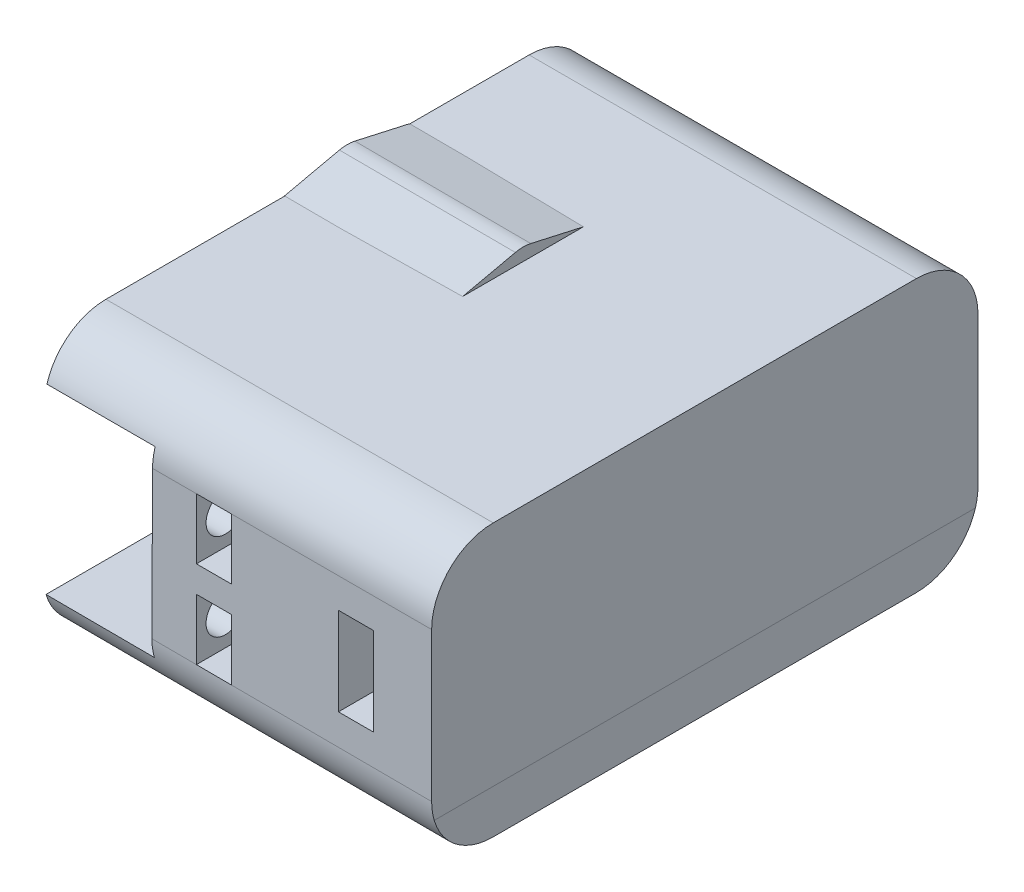
SolidWorks part; units mm, degrees
ref_plane "Front Plane" through (0, 0, 0) normal (0, 0, 1) x (1, 0, 0)
ref_plane "Top Plane" through (0, 0, 0) normal (0, 1, 0) x (1, 0, 0)
ref_plane "Right Plane" through (0, 0, 0) normal (1, 0, 0) x (0, 0, -1)
sketch "Sketch1" plane through (0, 0, 0) normal (0, 0, 1) x (1, 0, 0)
  line L0 (-9.8, -9.9) -> (14.6672, -10)
  line L1 (-9.8, -10) -> (20.4, -10) construction
  line L2 (14.6672, -10) -> (14.6672, 10)
  line L3 (-9.8, 10) -> (20.4, 10) construction
  line L4 (14.6672, 10) -> (-9.8, 10)
  line L5 (-9.8, 10) -> (-9.8, -9.9)
  circle A0 centre (-9.8, 0) radius 9.9 construction
extrude "Boss-Extrude1" add sketch "Sketch1" along normal blind 8
sketch "Sketch3" plane through (-9.8, 0, 0) normal (-1, 0, 0) x (0, 0, 1)
  line L1 (0, -10) -> (8, -10)
  line L2 (0, -10) -> (0, 10)
  line L3 (0, 10) -> (8, 10)
  line L4 (8, -10) -> (8, 10)
extrude "Boss-Extrude2" add sketch "Sketch3" along normal up to surface (11.4498 mm away)
sketch "Sketch4" plane through (0, 0, 8) normal (0, 0, 1) x (1, 0, 0)
  line L0 (14.6672, 10) -> (-8.8505, 10)
  line L1 (14.6672, 10) -> (-21.1681, 10) construction
  line L2 (-8.8505, 10) -> (-8.8505, -9.9039)
  line L3 (-9.8, -9.9) -> (14.6672, -10) construction
  line L4 (-8.8505, -9.9039) -> (14.6672, -10)
  line L5 (14.6672, -10) -> (14.6672, 10)
extrude "Boss-Extrude3" add sketch "Sketch4" along normal offset from surface (6 mm away) 0.3
sketch "Sketch5" plane through (0, 0, 0) normal (0, 0, -1) x (-1, 0, 0)
  circle A0 centre (9.8, 7) radius 1.5
  circle A1 centre (16.6008, 0.1992) radius 1.5
  circle A2 centre (2.9992, 0.1992) radius 1.5
  circle A3 centre (9.8, -6.6015) radius 1.5
extrude "Cut-Extrude1" cut sketch "Sketch5" against normal blind 30
sketch "Sketch6" plane through (0, 0, 8) normal (0, 0, 1) x (1, 0, 0)
  circle A0 centre (-9.8, -6.6015) radius 1.8722
  circle A1 centre (-2.9992, 0.1992) radius 2.25
  circle A2 centre (-16.6008, 0.1992) radius 2.25
  circle A3 centre (-9.8, 7) radius 2.25
  circle A4 centre (-9.8, 0) radius 2.8009
extrude "Cut-Extrude2" cut sketch "Sketch6" against normal blind 2.5 and the other way blind 30
sketch "Sketch7" plane through (0, 0, 8) normal (0, 0, 1) x (1, 0, 0)
  circle A0 centre (-9.8, 0) radius 2.8009
extrude "Cut-Extrude3" cut sketch "Sketch7" against normal blind 32.5
sketch "Sketch8" plane through (-0.0406, -9.9399, 0) normal (-0.0041, -1, 0) x (-1, 0.0041, 0)
  line L0 (21.2087, -8) -> (21.2087, -14)
  line L1 (21.2087, -14) -> (-17.8113, -14)
  line L2 (-17.8113, -14) -> (-17.8113, 0)
  line L3 (-17.8113, 0) -> (21.2087, 0)
  line L4 (21.2087, 0) -> (21.2087, -8)
extrude "Boss-Extrude4" add sketch "Sketch8" along normal blind 0.45
sketch "Sketch9" plane through (-0.0406, -9.9399, 0) normal (0.0041, 1, 0) x (1, -0.0041, 0)
  line L1 (14.6262, 0) -> (17.8113, 0)
  line L2 (14.6262, 0) -> (14.6262, -14)
  line L3 (14.6262, -14) -> (17.8113, -14)
  line L4 (17.8113, 0) -> (17.8113, -14)
extrude "Boss-Extrude5" add sketch "Sketch9" along normal up to surface (20.0129 mm away)
sketch "Sketch10" plane through (0, 10, 0) normal (0, 1, 0) x (1, 0, 0)
  line L5 (-21.1681, 0) -> (17.8523, 0)
  line L6 (-21.1681, 0) -> (-21.1681, -14)
  line L7 (-21.1681, -14) -> (17.8523, -14)
  line L8 (17.8523, 0) -> (17.8523, -14)
extrude "Boss-Extrude6" add sketch "Sketch10" along normal blind 0.45
sketch "Sketch11" plane through (0, 10.45, 0) normal (0, 1, 0) x (1, 0, 0)
  line L0 (-21.1681, 0) -> (17.8523, 0)
  line L1 (17.8523, 0) -> (22.8523, 0)
  line L2 (22.8523, 0) -> (22.8523, -55.1)
  line L5 (17.7505, -62.1) -> (22.8523, -62.1)
  line L6 (22.8523, -62.1) -> (22.8523, -55.1)
  line L7 (17.7505, -62.1) -> (-21.1681, -62.1)
  line L8 (-21.1681, -62.1) -> (-21.1681, 0)
extrude "Boss-Extrude7" add sketch "Sketch11" along normal blind 5
sketch "Sketch12" plane through (0, 10.45, 0) normal (0, -1, 0) x (-1, 0, 0)
  line L0 (-22.8523, 0) -> (-18.1523, 0)
  line L1 (-22.8523, 0) -> (-17.8523, 0) construction
  line L2 (-18.1523, 0) -> (-18.1523, -62.1)
  line L3 (21.1681, -62.1) -> (-22.8523, -62.1) construction
  line L4 (-18.1523, -62.1) -> (-22.8523, -62.1)
  line L5 (-22.8523, -62.1) -> (-22.8523, 0)
extrude "Boss-Extrude8" add sketch "Sketch12" along normal up to surface (20.9335 mm away)
sketch "Sketch13" plane through (-0.0425, -10.3899, 0) normal (-0.0041, -1, 0) x (-1, 0.0041, 0)
  line L0 (8.9087, -61.4) -> (8.9087, -62.1)
  line L1 (21.2106, -62.1) -> (-18.1094, -62.1) construction
  line L2 (8.9087, -62.1) -> (-17.7913, -62.1)
  line L4 (-17.7913, -55.6577) -> (8.9087, -55.6577)
  line L5 (8.9087, -55.1) -> (8.9087, -61.4) construction
  line L6 (8.9087, -55.6577) -> (8.9087, -61.4)
  line L7 (-17.7913, -55.6577) -> (-18.1949, -55.6577)
  line L8 (-18.1949, 0) -> (-18.1949, -62.1) construction
  line L9 (-18.1949, -55.6577) -> (-18.1949, -62.1)
  line L10 (-18.1949, -62.1) -> (-17.7913, -62.1)
extrude "Boss-Extrude10" add sketch "Sketch13" against normal up to surface (20.8036 mm away)
sketch "Sketch15" plane through (-0.0425, -10.3899, 0) normal (-0.0041, -1, 0) x (1, -0.0041, 0)
  line L0 (17.8113, 14) -> (18.1949, 14)
  line L1 (18.1949, 0) -> (18.1949, 55.6577) construction
  line L2 (18.1949, 14) -> (18.1949, 0)
  line L3 (18.1949, 0) -> (17.8113, 0)
  line L4 (17.8113, 0) -> (17.8113, 14)
extrude "Boss-Extrude12" add sketch "Sketch15" against normal up to surface (20.9129 mm away)
sketch "Sketch16" plane through (-0.0425, -10.3899, 0) normal (-0.0041, -1, 0) x (-1, 0.0041, 0)
  line L1 (-22.8949, 0) -> (21.231, 0)
  line L2 (-22.8949, 0) -> (-22.8949, -62.1)
  line L3 (-22.8949, -62.1) -> (21.231, -62.1)
  line L4 (21.231, 0) -> (21.231, -62.1)
extrude "Boss-Extrude13" add sketch "Sketch16" along normal blind 5
fillet "Fillet1" radius 7 4 edges at (0.8421, 15.45, 62.1) (0.769, -15.3932, 62.1) (0.8421, 15.45, 0) (0.769, -15.3932, 0)
sketch "Sketch17" plane through (-8.9087, 0.0364, 0) normal (-1, 0.0041, 0) x (0, 0, 1)
  circle A0 centre (58.8, -4.89) radius 2.2
  circle A1 centre (58.8, 5.01) radius 2.2
extrude "Cut-Extrude8" cut sketch "Sketch17" against normal blind 20
sketch "Sketch18" plane through (0, 0, 62.1) normal (0, 0, 1) x (1, 0, 0)
  line L0 (-14.0426, 5.0675) -> (-8.8882, 5.0464)
  line L1 (-14.0336, 7.2674) -> (-14.0516, 2.8675) construction
  line L2 (-8.8743, 8.45) -> (-8.943, -8.3535) construction
  line L3 (-3.8882, -8.4499) -> (-3.8882, -4.9499)
  line L4 (-3.8882, 5.0464) -> (-3.8882, 1.5464)
  line L5 (-3.8882, 1.5464) -> (0.1118, 1.5464)
  line L6 (0.1118, 1.5464) -> (0.1118, 8.5464)
  line L7 (0.1118, 8.5464) -> (-3.8882, 8.5464)
  line L8 (-3.8882, 8.5464) -> (-3.8882, 5.0464)
  line L9 (-8.9086, 0.0483) -> (-6.0294, 0.0483)
  line L10 (0.1118, -8.4499) -> (-3.8882, -8.4499)
  line L11 (0.1118, -1.4499) -> (0.1118, -8.4499)
  line L12 (-3.8882, -1.4499) -> (0.1118, -1.4499)
  line L13 (-3.8882, -4.9499) -> (-3.8882, -1.4499)
  line M8 (22.8523, 8.45) -> (-8.8743, 8.45)
  line M10 (-8.943, -8.3535) -> (22.8523, -8.4834)
extrude "Cut-Extrude9" cut sketch "Sketch18" against normal blind 20 contours L13 L3 L11 L12 M10 | L8 L4 L5 L6 M8
sketch "Sketch19" plane through (-21.2308, 0.0868, 0) normal (-1, 0.0041, 0) x (0, 0, 1)
  line L0 (27.6923, -15.39) -> (27.6923, -10.39)
  line L1 (55.1, -15.39) -> (7, -15.39) construction
  line L2 (61.8082, -10.39) -> (0.2918, -10.39) construction
  line L3 (26.8159, -16.7901) -> (20.585, -15.39)
  line L4 (28.5687, -16.7901) -> (34.7995, -15.39)
  line L5 (34.7995, -15.39) -> (20.585, -15.39)
  line L6 (61.3994, 0) -> (18.835, 0)
  line L7 (34.7995, 15.39) -> (20.585, 15.39)
  line L8 (28.5687, 16.7901) -> (34.7995, 15.39)
  line L9 (26.8159, 16.7901) -> (20.585, 15.39)
  line L10 (27.6923, 15.39) -> (27.6923, 10.39)
  circle A0 centre (27.6923, -12.89) radius 1.7
  arc A1 (26.8159, -16.7901) -> (28.5687, -16.7901) centre (27.6923, -12.89) ccw
  arc A2 (26.8159, 16.7901) -> (28.5687, 16.7901) centre (27.6923, 12.89) cw
  circle A3 centre (27.6923, 12.89) radius 1.7
  line M8 (7, -15.39) -> (55.1, -15.39)
extrude "Boss-Extrude14" add sketch "Sketch19" against normal blind 20 contours L3 A1 L4 M8 | A2 L9 L7 L8
sketch "Sketch20" plane through (-21.2308, 0.0868, 0) normal (-1, 0.0041, 0) x (0, 0, 1)
  line L0 (33.8933, 0) -> (17.4066, 0)
  circle A0 centre (27.6923, 12.89) radius 1.7
  circle A1 centre (27.6923, -12.89) radius 1.7
extrude "Cut-Extrude10" cut sketch "Sketch20" against normal blind 20 contours A1 | A0
sketch "Sketch21" plane through (0, 0, 62.1) normal (0, 0, 1) x (1, 0, 0)
  line L0 (-8.9086, 0.0483) -> (14.253, 0.0483)
  line L1 (-8.8743, 8.45) -> (-8.943, -8.3535) construction
  line L3 (16.253, -4.9517) -> (12.253, -4.9517)
  line L4 (16.253, -4.9517) -> (16.253, 5.0483)
  line L5 (16.253, 5.0483) -> (12.253, 5.0483)
  line L6 (12.253, -4.9517) -> (12.253, 5.0483)
  line L7 (16.253, -4.9517) -> (12.253, 5.0483) construction
  line L8 (16.253, 5.0483) -> (12.253, -4.9517) construction
extrude "Cut-Extrude11" cut sketch "Sketch21" against normal blind 11
